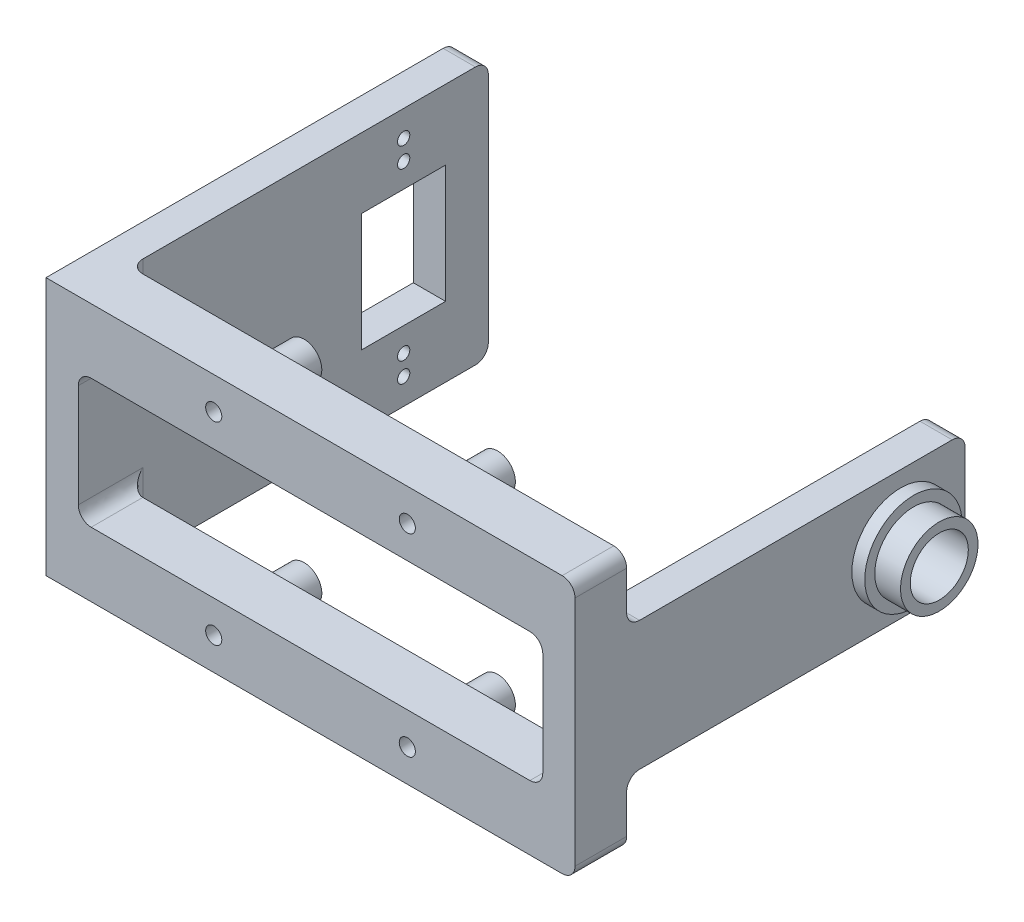
SolidWorks part; units mm, degrees
ref_plane "Front Plane" through (0, 0, 0) normal (0, 0, 1) x (1, 0, 0)
ref_plane "Top Plane" through (0, 0, 0) normal (0, 1, 0) x (1, 0, 0)
ref_plane "Right Plane" through (0, 0, 0) normal (1, 0, 0) x (0, 0, -1)
sketch "Sketch1" plane through (0, 0, 0) normal (1, 0, 0) x (0, 0, -1)
  line L1 (0, 0) -> (60.45, 0)
  line L2 (0, 0) -> (0, 20)
  line L3 (0, 20) -> (60.45, 20)
  line L4 (60.45, 0) -> (60.45, 20)
  dimension "D1" = 60.45
  dimension "D2" = 20
extrude "Boss-Extrude1" add sketch "Sketch1" along normal blind 5
sketch "Sketch2" plane through (5, 0, 0) normal (1, 0, 0) x (0, 0, -1)
  line L1 (60.45, 0) -> (60.45, 20) construction
  circle A0 centre (50.45, 10) radius 7.545
  point P5 (60.45, 10)
  dimension "D1" = 15.09
  dimension "D2" = 10
extrude "Boss-Extrude2" add sketch "Sketch2" along normal blind 2
sketch "Sketch3" plane through (7, 0, 0) normal (1, 0, 0) x (0, 0, -1)
  circle A0 centre (50.45, 10) radius 6
  circle A1 centre (50.45, 10) radius 7.545 construction
  dimension "D1" = 12
extrude "Boss-Extrude3" add sketch "Sketch3" along normal blind 4
sketch "Sketch4" plane through (11, 0, 0) normal (1, 0, 0) x (0, 0, -1)
  circle A0 centre (50.45, 10) radius 4.5
  circle A1 centre (50.45, 10) radius 6 construction
  dimension "D1" = 9
extrude "Cut-Extrude1" cut sketch "Sketch4" against normal up to next
sketch "Sketch5" plane through (5, 0, 0) normal (1, 0, 0) x (0, 0, -1)
  line L1 (0, 20) -> (8, 20)
  line L2 (0, 20) -> (0, 30)
  line L3 (0, 30) -> (8, 30)
  line L4 (8, 20) -> (8, 30)
  line L5 (0, 0) -> (8, 0)
  line L6 (0, 0) -> (0, -10)
  line L7 (0, -10) -> (8, -10)
  line L8 (8, 0) -> (8, -10)
  dimension "D1" = 10
  dimension "D2" = 8
extrude "Boss-Extrude4" add sketch "Sketch5" against normal blind 81.99
sketch "Sketch6" plane through (0, 0, -8) normal (0, 0, -1) x (-1, 0, 0)
  line L1 (76.99, -10) -> (71.99, -10)
  line L2 (76.99, -10) -> (76.99, 30)
  line L3 (76.99, 30) -> (71.99, 30)
  line L4 (71.99, -10) -> (71.99, 30)
  dimension "D1" = 5
extrude "Boss-Extrude5" add sketch "Sketch6" along normal blind 55.55 and the other way blind 8
ref_plane "Plane1" through (-35.995, 0, 0) normal (-1, 0, 0) x (0, 0, 1)
ref_plane "Plane2" through (0, 10, 0) normal (0, -1, 0) x (-1, 0, 0)
sketch "Sketch7" plane through (0, 0, -8) normal (0, 0, -1) x (-1, 0, 0)
  line L1 (35.995, -22) -> (35.995, 22) construction
  line L2 (-4.4, 10) -> (4.4, 10) construction
  line L3 (71.99, 20) -> (0, 20) construction
  circle A0 centre (20.995, 24.99) radius 2.75
  circle A1 centre (50.995, 24.99) radius 2.75
  circle A2 centre (50.995, -4.99) radius 2.75
  circle A3 centre (20.995, -4.99) radius 2.75
  dimension "D1" = 5.5
  dimension "D2" = 15
  dimension "D3" = 4.99
extrude "Boss-Extrude6" add sketch "Sketch7" along normal blind 6
sketch "Sketch8" plane through (0, 0, -14) normal (0, 0, -1) x (-1, 0, 0)
  line L0 (35.995, -22) -> (35.995, 22) construction
  line L1 (-4.4, 10) -> (4.4, 10) construction
  circle A0 centre (20.995, 24.99) radius 1.25
  circle A1 centre (20.995, 24.99) radius 2.75 construction
  circle A2 centre (50.995, 24.99) radius 1.25
  circle A3 centre (50.995, -4.99) radius 1.25
  circle A4 centre (20.995, -4.99) radius 1.25
  dimension "D1" = 2.5
extrude "Cut-Extrude2" cut sketch "Sketch8" against normal up to next
sketch "Sketch9" plane through (-76.99, 0, 0) normal (-1, 0, 0) x (0, 0, 1)
  line L0 (-50.43, 30) -> (-50.43, -10) construction
  line L1 (-63.55, 30) -> (0, 30) construction
  line L2 (0, -10) -> (-63.55, -10) construction
  line L3 (0, 30) -> (0, -10) construction
  line L5 (-56.93, 19.15) -> (-43.93, 19.15)
  line L6 (-56.93, 19.15) -> (-56.93, 0.85)
  line L7 (-56.93, 0.85) -> (-43.93, 0.85)
  line L8 (-43.93, 19.15) -> (-43.93, 0.85)
  circle A0 centre (-50.43, 22.88) radius 0.95
  circle A1 centre (-50.43, -2.88) radius 0.95
  circle A2 centre (-50.43, -5.98) radius 0.95
  circle A3 centre (-50.43, 25.98) radius 0.95
  point P12 (-50.43, 19.15)
  dimension "D5" = 1.9
  dimension "D1" = 50.43
  dimension "D2" = 18.3
  dimension "D3" = 13
  dimension "D4" = 10.85
  dimension "D6" = 3.73
  dimension "D7" = 3.73
  dimension "D8" = 3.1
  dimension "D9" = 3.1
extrude "Cut-Extrude3" cut sketch "Sketch9" against normal up to next
fillet "Fillet1" radius 2 12 edges at (-74.49, 30, -63.55) (-74.49, -10, -63.55) (-71.99, 20, -4) (-71.99, 0, -4) (-71.99, -5, -8) (-71.99, 25, -8) (5, -10, -4) (5, 30, -4) (2.5, 0, -60.45) (2.5, 20, -60.45) (0, 0, -4) (0, 20, -4) first distance on face at (-47.9933, 30, -23.85) first distance on face at (-47.9933, -10, -23.85) first distance on face at (-35.995, 20, -4) first distance on face at (-35.995, 0, -4) first distance on face at (-18.245, -4.99, -8) first distance on face at (-48.245, 24.99, -8) first distance on face at (2.5, 10, -60.45) first distance on face at (0, 10, -45.95)
fillet "Fillet2" radius 2 2 edges at (2.5, 20, -8) (2.5, 0, -8) first distance on face at (-48.245, 24.99, -8) first distance on face at (1.875, 0, -33.225)
